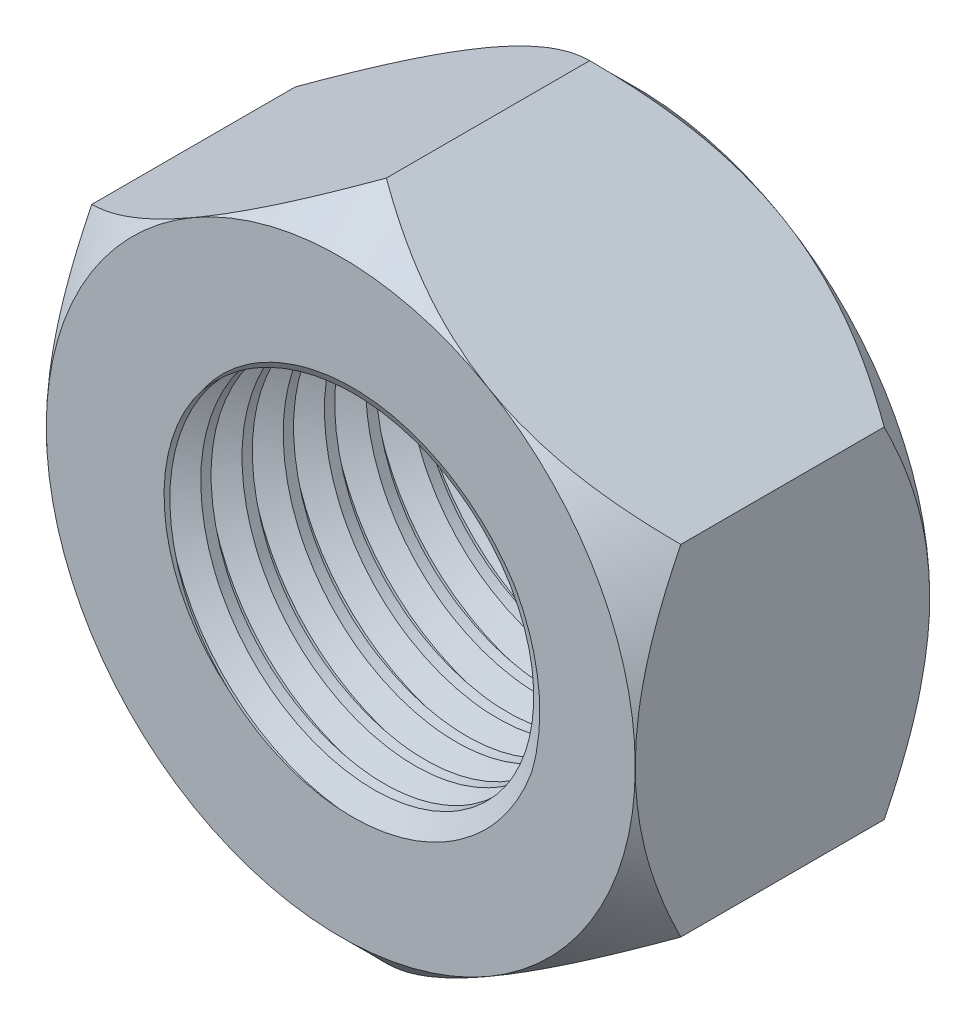
SolidWorks part; units mm, degrees
material "Cast Stainless Steel"
ref_plane "Front Plane" through (0, 0, 0) normal (0, 0, 1) x (1, 0, 0)
ref_plane "Top Plane" through (0, 0, 0) normal (0, 1, 0) x (1, 0, 0)
ref_plane "Right Plane" through (0, 0, 0) normal (1, 0, 0) x (0, 0, -1)
sketch "Sketch1" plane through (0, 0, 0) normal (0, 0, 1) x (1, 0, 0)
  line L0 (0, 0) -> (0, 3.9416) construction
  line L1 (0, 2.8868) -> (-2.5, 1.4434)
  line L2 (-2.5, 1.4434) -> (-2.5, -1.4434)
  line L3 (-2.5, -1.4434) -> (0, -2.8868)
  line L4 (0, -2.8868) -> (2.5, -1.4434)
  line L5 (2.5, -1.4434) -> (2.5, 1.4434)
  line L6 (2.5, 1.4434) -> (0, 2.8868)
  circle A0 centre (0, 0) radius 2.5 construction
  circle A1 centre (0, 0) radius 1.5
  dimension "D1" = 5
  dimension "D2" = 3
extrude "Boss-Extrude1" add sketch "Sketch1" along normal mid plane 2.5 contours L6 L1 L2 L3 L4 L5
sketch "Sketch8" plane through (0, 0, 1.25) normal (0, 0, 1) x (1, 0, 0)
  circle A0 centre (0, 0) radius 2.5
  dimension "D1" = 5
extrude "Cut-Extrude4" cut sketch "Sketch8" against normal blind 10 draft 45 flip side to cut
mirror "Mirror1" about plane through (0, 0, 0) normal (0, 0, 1) of "Cut-Extrude4"
extrude "Cut-Extrude5" cut sketch "Sketch1<4>" against normal blind 10 and the other way blind 10 contours A1
sketch "Sketch1<4>" plane through (0, 0, 0) normal (0, 0, 1) x (1, 0, 0) same geometry as "Sketch1"
thread "Thread2" pitch 0.35 method cut profile "Thread Profile3" start angle 0, offset 1, length 10, pitch 0.35, diameter 3
ref_plane "Plane3" through (-1.5, 0, 2.25) normal (0, -1, 0) x (-1, 0, 0)
sketch "Thread Profile3" plane through (-1.5, 0, 2.25) normal (0, -1, 0) x (-1, 0, 0)
  line L0 (0, 0) -> (0, 0.35) construction
  line L1 (0, 0) -> (0.1894, 0.1094)
  line L2 (0.1894, 0.1094) -> (0.1894, 0.1531)
  line L3 (0.1894, 0.1531) -> (0, 0.2625)
  line L4 (0.1894, 0.1312) -> (0, 0.1312) construction
  line L11 (0, 0) -> (0, 0.2625)
  point P2 (0, 0)
  dimension "Pitch" = 0.35
  dimension "Profile_Angle" = 60
  dimension "Profile_Land" = 0.0437
  dimension "Profile_Height" = 0.1894
